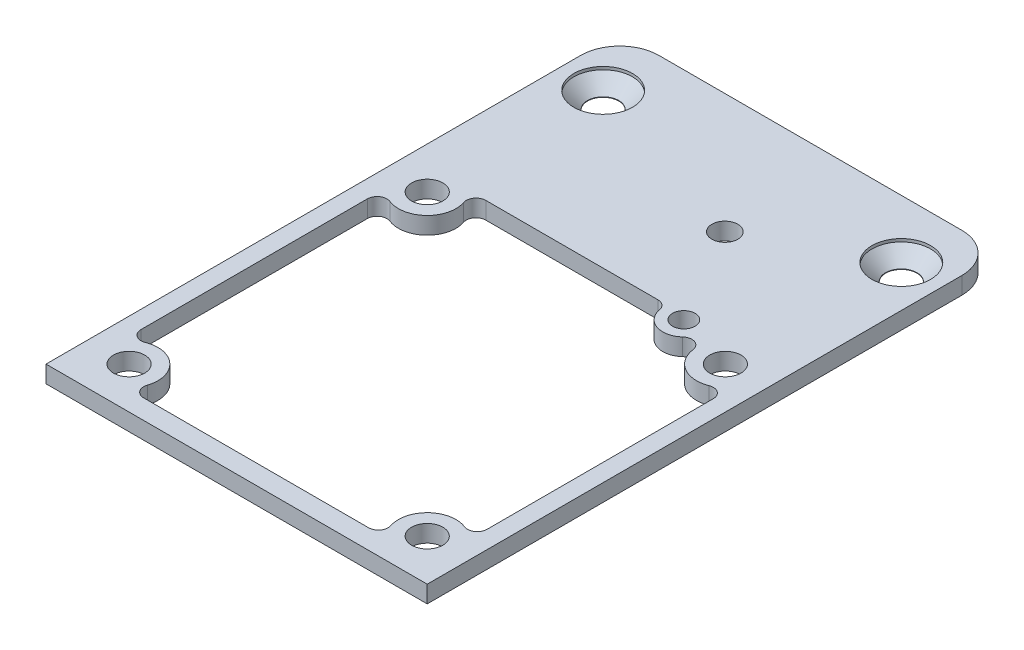
SolidWorks part; units mm, degrees
ref_plane "Front Plane" through (0, 0, 0) normal (0, 0, 1) x (1, 0, 0)
ref_plane "Top Plane" through (0, 0, 0) normal (0, 1, 0) x (1, 0, 0)
ref_plane "Right Plane" through (0, 0, 0) normal (1, 0, 0) x (0, 0, -1)
sketch "Sketch1" plane through (0, 0, 0) normal (0, 1, 0) x (1, 0, 0)
  line L0 (-15.5, 39.2) -> (15.5, 39.2)
  line L1 (-18.2, 15) -> (-18.2, -15) construction
  line L2 (17.7, -17.4996) -> (-17.7, -17.4996)
  line L3 (17.7, -17.4996) -> (17.7, 17.4996)
  line L4 (17.7, 17.4996) -> (-17.7, 17.4996)
  line L5 (-17.7, -17.4996) -> (-17.7, 17.4996)
  line L6 (17.7, -17.4996) -> (-17.7, 17.4996) construction
  line L7 (-19.5, 35.2) -> (-19.5, -19.5)
  line L8 (-19.5, -19.5) -> (19.5, -19.5)
  line L9 (19.5, -19.5) -> (19.5, 35.2)
  line L10 (17.7, 17.4996) -> (-17.7, -17.4996) construction
  line L11 (-15.25, 15.25) -> (-15.25, 17.9996) construction
  line L12 (11.35, 17.05) -> (11.35, 17.4996)
  line L13 (7.05, 17.05) -> (7.05, 17.4996)
  arc A0 (19.5, 35.2) -> (15.5, 39.2) centre (15.5, 35.2) ccw construction
  arc A1 (-15.5, 39.2) -> (-19.5, 35.2) centre (-15.5, 35.2) ccw construction
  arc A2 (19.5, 35.2) -> (15.5, 39.2) centre (15.5, 35.2) ccw
  arc A3 (-15.5, 39.2) -> (-19.5, 35.2) centre (-15.5, 35.2) ccw
  circle A4 centre (-15.25, -15.25) radius 1.6 construction
  circle A5 centre (15.25, -15.25) radius 1.6 construction
  circle A6 centre (-15.25, 15.25) radius 1.6 construction
  circle A7 centre (15.25, 15.25) radius 1.6 construction
  circle A8 centre (-15.25, 33.25) radius 1.6 construction
  circle A9 centre (15.25, 33.25) radius 1.6 construction
  circle A10 centre (-15.25, -15.25) radius 1.6
  circle A11 centre (15.25, -15.25) radius 1.6
  circle A12 centre (-15.25, 15.25) radius 1.6
  circle A13 centre (15.25, 15.25) radius 1.6
  circle A14 centre (-15.25, 33.25) radius 1.6
  circle A15 centre (15.25, 33.25) radius 1.6
  arc A16 (-15.2, 18) -> (-18.2, 15) centre (-15.2, 15) ccw construction
  circle A17 centre (-15.25, 15.25) radius 2.95
  circle A18 centre (15.25, 15.25) radius 2.95
  circle A19 centre (-15.25, -15.25) radius 2.95
  circle A20 centre (15.25, -15.25) radius 2.95
  circle A21 centre (3.5, 26.95) radius 1.33 construction
  circle A22 centre (9.2, 17.05) radius 2.15
  circle A23 centre (9.2, 17.05) radius 1.15
  circle A24 centre (9.2, 17.05) radius 0.9 construction
  circle A25 centre (3.5, 26.95) radius 1.33
  circle A26 centre (11.334, 14.733) radius 1
  point P29 (0, 0)
  dimension "D3" = 2.3
  dimension "D4" = 1
  dimension "D5" = 2
  dimension "D1" = 0.5
  dimension "D2" = 0.5
extrude "Base shape" add sketch "Sketch1" along normal blind 1.75 contours L0 A3 L7 L8 L9 A2 A20 L3 L2 A19 L5 A17 L4 A18 A15 A14 | A17 L4 L5 | L4 A17 L5 A12 | L5 A17 | L4 A17 | L3 A18 L4 A13 | L3 A18 | L4 A18 | L2 A19 L5 A10 | L2 A19 | L5 A19 | A19 L5 L2 | L2 A20 L3 A11 | L3 A20 | L2 A20 | A20 L2 L3 | A18 L3 L4 | A23 L4 A22 | A23 L4 A22 | A22 L4 L13 | A22 L12 L4 | A26 A18 L4 L12 A22 region at (-0.0683, 0, -21.4041) region at (17.5279, 0, 17.307) region at (15.25, 0, 17.7828) region at (15.25, 0, 17.4246) region at (17.9015, 0, 15.25) region at (-15.25, 0, 17.7828) region at (-15.25, 0, 17.4246) region at (14.5952, 0, -12.4505) region at (17.9015, 0, -15.25) region at (-17.5279, 0, 17.307) region at (17.5279, 0, -17.307) region at (11.9929, 0, -16.5859) region at (-17.9015, 0, 15.25) region at (15.25, 0, -17.7828) region at (8.3568, 0, -15.127) region at (-17.9015, 0, -15.25) region at (-17.625, 0, -15.25) region at (11.3358, 0, -17.3874) region at (7.0642, 0, -17.3874) region at (-17.5279, 0, -17.307) region at (9.2, 0, -18.3154) region at (-15.25, 0, -17.7828)
fillet "Milling fillets" radius 1 8 edges at (-17.7, 0.875, 13.6068) (-13.3416, 0.875, 17.4996) (13.3416, 0.875, 17.4996) (17.7, 0.875, 13.6068) (17.7, 0.875, -13.6068) (-13.3416, 0.875, -17.4996) (-17.7, 0.875, -13.6068) (7.05, 0.875, -17.4996)
sketch "Sketch3" plane through (0, 1.75, 0) normal (0, 1, 0) x (1, 0, 0)
  circle A0 centre (-15.25, 33.25) radius 3
  circle A1 centre (15.25, 33.25) radius 3
  dimension "D1" = 6
extrude "Screw head cut" cut sketch "Sketch3" against normal blind 0.3
chamfer "Screw head chamfer" distance 1.4 angle 45 2 edges at (15.25, 1.45, -31.65) (-15.25, 1.45, -31.65)
